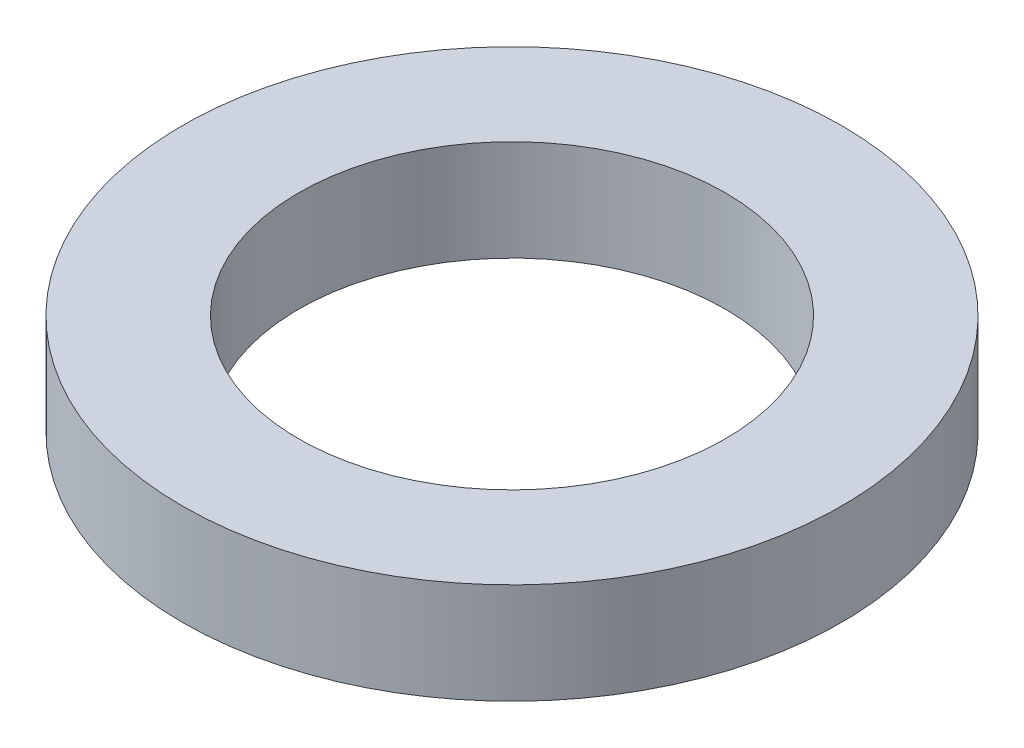
SolidWorks part; units mm, degrees
ref_plane "Front Plane" through (0, 0, 0) normal (0, 0, 1) x (1, 0, 0)
ref_plane "Top Plane" through (0, 0, 0) normal (0, 1, 0) x (1, 0, 0)
ref_plane "Right Plane" through (0, 0, 0) normal (1, 0, 0) x (0, 0, -1)
sketch "Sketch1" plane through (0, 0, 0) normal (0, 1, 0) x (1, 0, 0)
  circle A0 centre (0, 0) radius 42.5
  dimension "FLANGE_OD" = 85
extrude "Boss-Extrude1" add sketch "Sketch1" along normal blind 13
sketch "Sketch2" plane through (0, 0, 0) normal (0, 1, 0) x (1, 0, 0)
  circle A0 centre (0, 0) radius 27.5
  dimension "BORE_D" = 55
extrude "Cut-Extrude1" cut sketch "Sketch2" along normal through all
sketch "Sketch3" plane through (0, 13, 0) normal (0, 1, 0) x (1, 0, 0)
  circle A0 centre (0, 0) radius 16.2835 construction
  circle A1 centre (-16.2835, 0) radius 2.4013
  dimension "BOLT_D" = 4.8026
  dimension "BOLT_PCD" = 32.567
extrude "Cut-Extrude2" cut sketch "Sketch3" against normal blind 10.4688 rebuild error yes
pattern_circular "CirPattern1" count 3 over 360 rebuild error yes
